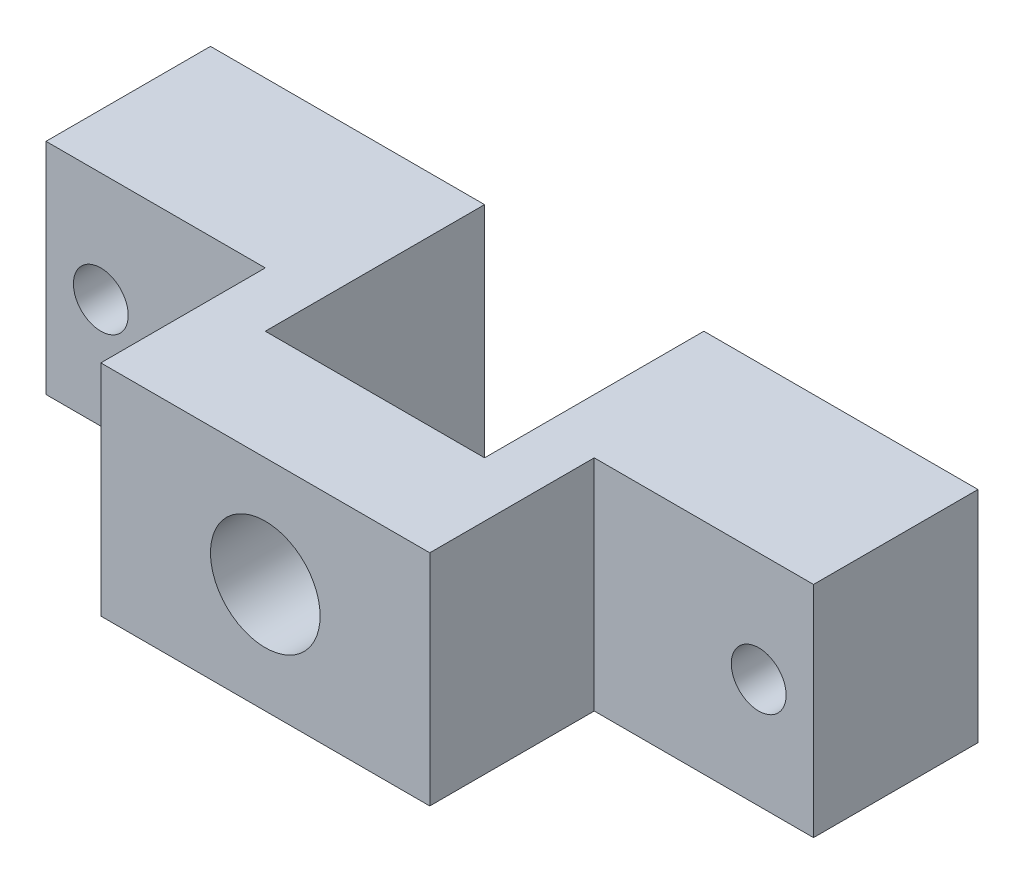
SolidWorks part; units mm, degrees
ref_plane "Front Plane" through (0, 0, 0) normal (0, 0, 1) x (1, 0, 0)
ref_plane "Top Plane" through (0, 0, 0) normal (0, 1, 0) x (1, 0, 0)
ref_plane "Right Plane" through (0, 0, 0) normal (1, 0, 0) x (0, 0, -1)
sketch "Sketch1" plane through (0, 0, 0) normal (0, 0, 1) x (1, 0, 0)
  line L1 (0, 0) -> (70, 0)
  line L2 (0, 0) -> (0, 20)
  line L3 (0, 20) -> (70, 20)
  line L4 (70, 0) -> (70, 20)
  circle A1 centre (65, 10) radius 2.5
  circle A2 centre (5, 10) radius 2.5
  point P4 (0, 0)
  point P11 (178.8347, 10)
  point P12 (0, 0)
  point P13 (191.6205, 10)
  point P14 (167.632, 10)
  point P15 (0, 0)
  point P16 (0, 0)
  point P17 (0, 0)
  point P18 (61.9101, 10)
  point P19 (33.6139, 10)
  point P23 (0, 0)
  dimension "D1" = 70
  dimension "D2" = 20
extrude "Boss-Extrude1" add sketch "Sketch1" along normal blind 15
sketch "Sketch2" plane through (0, 0, 15) normal (0, 0, 1) x (1, 0, 0)
  line L0 (0, 0) -> (70, 0) construction
  line L1 (20, 0) -> (50, 0)
  line L2 (20, 0) -> (20, 20)
  line L3 (20, 20) -> (50, 20)
  line L4 (50, 0) -> (50, 20)
  line L5 (70, 20) -> (0, 20) construction
extrude "Boss-Extrude2" add sketch "Sketch2" along normal blind 15
sketch "Sketch4" plane through (0, 20, 0) normal (0, 1, 0) x (1, 0, 0)
  line L0 (70, 0) -> (0, 0) construction
  line L1 (25, -20) -> (45, -20)
  line L2 (25, -20) -> (25, 0)
  line L3 (25, 0) -> (45, 0)
  line L4 (45, -20) -> (45, 0)
extrude "Cut-Extrude1" cut sketch "Sketch4" against normal through all
sketch "Sketch5" plane through (0, 0, 30) normal (0, 0, 1) x (1, 0, 0)
  circle A0 centre (35, 10) radius 5
  circle A1 centre (65, 10) radius 2.5 construction
  dimension "D1" = 30
extrude "Cut-Extrude2" cut sketch "Sketch5" against normal through all
